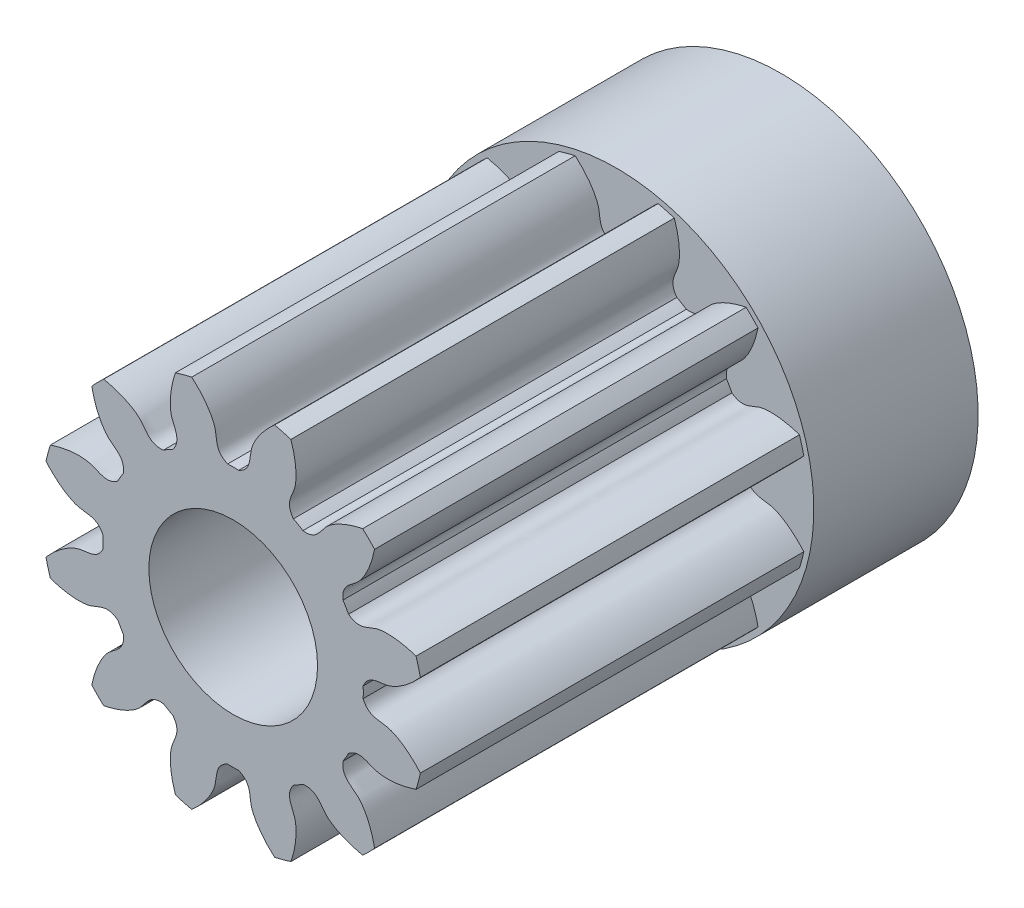
SolidWorks part; units mm, degrees
ref_plane "前视基准面" through (0, 0, 0) normal (0, 0, 1) x (1, 0, 0)
ref_plane "上视基准面" through (0, 0, 0) normal (0, 1, 0) x (1, 0, 0)
ref_plane "右视基准面" through (0, 0, 0) normal (1, 0, 0) x (0, 0, -1)
other "Configuration Table"
sketch "草图1" plane through (0, 0, 0) normal (0, 0, 1) x (1, 0, 0)
  circle A0 centre (0, 0) radius 3.5
extrude "凸台-拉伸1" add sketch "草图1" along normal blind 7
ref_axis "基准轴1" through (0, 0, 7) along (0, 0, -1)
sketch "草图2" plane through (0, 0, 0) normal (0, 0, 1) x (1, 0, 0)
  line L0 (0, 0) -> (0, 3.5) construction
  circle A0 centre (0, 0) radius 3.5 construction
  arc A1 (0.1004, 2.3729) -> (-0.1004, 2.3729) centre (0, 0) ccw
  arc A2 (1.7488, 3.9475) -> (-1.7488, 3.9475) centre (0, 0) ccw
  spline S0 degree 3 poles (0.1004, 2.3729) (0.3404, 2.4747) (0.2872, 2.6724) (0.3381, 2.8447) (0.3413, 2.855) (0.3451, 2.8662) (0.3495, 2.8784) (0.3546, 2.8915) (0.3603, 2.9056) (0.3668, 2.9206) (0.374, 2.9366) (0.3821, 2.9533) (0.3909, 2.971) (0.4007, 2.9894) (0.4114, 3.0086) (0.423, 3.0286) (0.4356, 3.0493) (0.4492, 3.0707) (0.4639, 3.0928) (0.4796, 3.1155) (0.4965, 3.1388) (0.5145, 3.1626) (0.5337, 3.187) (0.554, 3.2119) (0.5756, 3.2372) (0.5985, 3.2629) (0.6226, 3.289) (0.648, 3.3154) (0.6748, 3.342) (0.7028, 3.369) (0.7323, 3.3961) (0.7631, 3.4234) (0.7954, 3.4507) (0.829, 3.4782) (0.8641, 3.5057) (0.9006, 3.5331) (0.9385, 3.5604) (0.978, 3.5877) (1.0189, 3.6147) (1.0613, 3.6416) (1.1052, 3.6681) (1.1506, 3.6944) (1.1975, 3.7203) (1.2459, 3.7457) (1.2958, 3.7707) (1.3472, 3.7952) (1.4001, 3.8191) (1.4546, 3.8424) (1.5105, 3.865) (1.5679, 3.8869) (1.6472, 3.9154) (1.7078, 3.9351) (1.7488, 3.9475) knots 0 0 0 0 0.218015 0.222044 0.226546 0.231522 0.236972 0.242897 0.249295 0.256167 0.263513 0.271332 0.279626 0.288394 0.297636 0.307351 0.317541 0.328204 0.339341 0.350953 0.363038 0.375597 0.38863 0.402137 0.416118 0.430573 0.445502 0.460904 0.476781 0.493132 0.509956 0.527255 0.545027 0.563273 0.581994 0.601188 0.620856 0.640998 0.661614 0.682704 0.704268 0.726305 0.748817 0.771803 0.795262 0.819196 0.843603 0.868484 0.89384 0.919669 0.945972 1 1 1 1
  spline S1 degree 3 poles (-0.1004, 2.3729) (-0.3404, 2.4747) (-0.2872, 2.6724) (-0.3381, 2.8447) (-0.3413, 2.855) (-0.3451, 2.8662) (-0.3495, 2.8784) (-0.3546, 2.8915) (-0.3603, 2.9056) (-0.3668, 2.9206) (-0.374, 2.9366) (-0.3821, 2.9533) (-0.3909, 2.971) (-0.4007, 2.9894) (-0.4114, 3.0086) (-0.423, 3.0286) (-0.4356, 3.0493) (-0.4492, 3.0707) (-0.4639, 3.0928) (-0.4796, 3.1155) (-0.4965, 3.1388) (-0.5145, 3.1626) (-0.5337, 3.187) (-0.554, 3.2119) (-0.5756, 3.2372) (-0.5985, 3.2629) (-0.6226, 3.289) (-0.648, 3.3154) (-0.6748, 3.342) (-0.7028, 3.369) (-0.7323, 3.3961) (-0.7631, 3.4234) (-0.7954, 3.4507) (-0.829, 3.4782) (-0.8641, 3.5057) (-0.9006, 3.5331) (-0.9385, 3.5604) (-0.978, 3.5877) (-1.0189, 3.6147) (-1.0613, 3.6416) (-1.1052, 3.6681) (-1.1506, 3.6944) (-1.1975, 3.7203) (-1.2459, 3.7457) (-1.2958, 3.7707) (-1.3472, 3.7952) (-1.4001, 3.8191) (-1.4546, 3.8424) (-1.5105, 3.865) (-1.5679, 3.8869) (-1.6472, 3.9154) (-1.7078, 3.9351) (-1.7488, 3.9475) knots 0 0 0 0 0.218015 0.222044 0.226546 0.231522 0.236972 0.242897 0.249295 0.256167 0.263513 0.271332 0.279626 0.288394 0.297636 0.307351 0.317541 0.328204 0.339341 0.350953 0.363038 0.375597 0.38863 0.402137 0.416118 0.430573 0.445502 0.460904 0.476781 0.493132 0.509956 0.527255 0.545027 0.563273 0.581994 0.601188 0.620856 0.640998 0.661614 0.682704 0.704268 0.726305 0.748817 0.771803 0.795262 0.819196 0.843603 0.868484 0.89384 0.919669 0.945972 1 1 1 1
extrude "切除-拉伸1" cut sketch "草图2" along normal through all
pattern_circular "阵列(圆周)1" count 12 over 360 about axis through (0, 0, 7) along (0, 0, -1) of "切除-拉伸1"
sketch "草图3" plane through (0, 0, 0) normal (0, 0, 1) x (1, 0, 0)
  circle A0 centre (0, 0) radius 3 construction
  dimension "Dn" = 6
sketch "草图5" plane through (0, 0, 0) normal (0, 0, -1) x (-1, 0, 0)
  circle A0 centre (0, 0) radius 3.6
  dimension "D1" = 7.2
extrude "凸台-拉伸2" add sketch "草图5" along normal blind 3
sketch "草图4" plane through (0, 0, 7) normal (0, 0, 1) x (1, 0, 0)
  circle A0 centre (0, 0) radius 1.54
  dimension "D1" = 3.08
extrude "切除-拉伸2" cut sketch "草图4" against normal up to next
sketch "草图6" plane through (0, 0, 0) normal (0, 1, 0) x (1, 0, 0)
  line L0 (1.54, 3) -> (-1.54, 3) construction
  circle A0 centre (0, 1) radius 0.825
  dimension "D1" = 1.65
  dimension "D2" = 2
extrude "切除-拉伸3" cut sketch "草图6" against normal up to next
